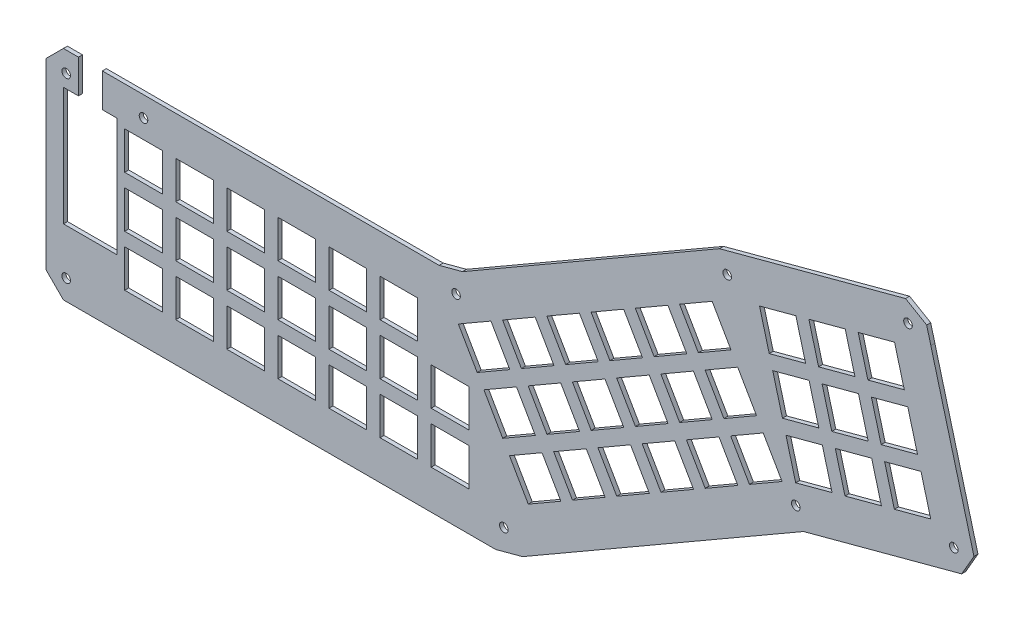
SolidWorks part; units mm, degrees
ref_plane "Plan de face" through (0, 0, 0) normal (0, 0, 1) x (1, 0, 0)
ref_plane "Plan de dessus" through (0, 0, 0) normal (0, 1, 0) x (1, 0, 0)
ref_plane "Plan de droite" through (0, 0, 0) normal (1, 0, 0) x (0, 0, -1)
sketch "Esquisse1" plane through (0, 0, 0) normal (0, 0, 1) x (1, 0, 0)
  line L0 (-73.9886, 18.0851) -> (-59.9886, 18.0851)
  line L1 (-73.9886, 37.0851) -> (-59.9886, 37.0851)
  line L2 (-73.9886, 37.0851) -> (-73.9886, 23.0851)
  line L3 (-73.9886, 23.0851) -> (-59.9886, 23.0851)
  line L4 (-59.9886, 37.0851) -> (-59.9886, 23.0851)
  line L5 (-73.9886, 18.0851) -> (-73.9886, 4.0851)
  line L6 (-73.9886, 4.0851) -> (-59.9886, 4.0851)
  line L7 (-59.9886, 18.0851) -> (-59.9886, 4.0851)
  line L8 (-73.9886, -0.9149) -> (-59.9886, -0.9149)
  line L9 (-73.9886, -0.9149) -> (-73.9886, -14.9149)
  line L10 (-73.9886, -14.9149) -> (-59.9886, -14.9149)
  line L11 (-59.9886, -0.9149) -> (-59.9886, -14.9149)
  line L12 (-73.9886, 37.0851) -> (-73.9886, 18.0851) construction
  line L13 (-54.9886, 18.0851) -> (-40.9886, 18.0851)
  line L14 (-54.9886, 37.0851) -> (-40.9886, 37.0851)
  line L15 (-54.9886, 37.0851) -> (-54.9886, 23.0851)
  line L16 (-54.9886, 23.0851) -> (-40.9886, 23.0851)
  line L17 (-40.9886, 37.0851) -> (-40.9886, 23.0851)
  line L18 (-54.9886, 18.0851) -> (-54.9886, 4.0851)
  line L19 (-54.9886, 4.0851) -> (-40.9886, 4.0851)
  line L20 (-40.9886, 18.0851) -> (-40.9886, 4.0851)
  line L21 (-54.9886, -0.9149) -> (-40.9886, -0.9149)
  line L22 (-54.9886, -0.9149) -> (-54.9886, -14.9149)
  line L23 (-54.9886, -14.9149) -> (-40.9886, -14.9149)
  line L24 (-40.9886, -0.9149) -> (-40.9886, -14.9149)
  line L25 (-54.9886, 37.0851) -> (-54.9886, 18.0851) construction
  line L26 (-35.9886, 18.0851) -> (-21.9886, 18.0851)
  line L27 (-35.9886, 37.0851) -> (-21.9886, 37.0851)
  line L28 (-35.9886, 37.0851) -> (-35.9886, 23.0851)
  line L29 (-35.9886, 23.0851) -> (-21.9886, 23.0851)
  line L30 (-21.9886, 37.0851) -> (-21.9886, 23.0851)
  line L31 (-35.9886, 18.0851) -> (-35.9886, 4.0851)
  line L32 (-35.9886, 4.0851) -> (-21.9886, 4.0851)
  line L33 (-21.9886, 18.0851) -> (-21.9886, 4.0851)
  line L34 (-35.9886, -0.9149) -> (-21.9886, -0.9149)
  line L35 (-35.9886, -0.9149) -> (-35.9886, -14.9149)
  line L36 (-35.9886, -14.9149) -> (-21.9886, -14.9149)
  line L37 (-21.9886, -0.9149) -> (-21.9886, -14.9149)
  line L38 (-35.9886, 37.0851) -> (-35.9886, 18.0851) construction
  line L39 (-16.9886, 18.0851) -> (-2.9886, 18.0851)
  line L40 (-16.9886, 37.0851) -> (-2.9886, 37.0851)
  line L41 (-16.9886, 37.0851) -> (-16.9886, 23.0851)
  line L42 (-16.9886, 23.0851) -> (-2.9886, 23.0851)
  line L43 (-2.9886, 37.0851) -> (-2.9886, 23.0851)
  line L44 (-16.9886, 18.0851) -> (-16.9886, 4.0851)
  line L45 (-16.9886, 4.0851) -> (-2.9886, 4.0851)
  line L46 (-2.9886, 18.0851) -> (-2.9886, 4.0851)
  line L47 (-16.9886, -0.9149) -> (-2.9886, -0.9149)
  line L48 (-16.9886, -0.9149) -> (-16.9886, -14.9149)
  line L49 (-16.9886, -14.9149) -> (-2.9886, -14.9149)
  line L50 (-2.9886, -0.9149) -> (-2.9886, -14.9149)
  line L51 (-16.9886, 37.0851) -> (-16.9886, 18.0851) construction
  line L52 (2.0114, 18.0851) -> (16.0114, 18.0851)
  line L53 (2.0114, 37.0851) -> (16.0114, 37.0851)
  line L54 (2.0114, 37.0851) -> (2.0114, 23.0851)
  line L55 (2.0114, 23.0851) -> (16.0114, 23.0851)
  line L56 (16.0114, 37.0851) -> (16.0114, 23.0851)
  line L57 (2.0114, 18.0851) -> (2.0114, 4.0851)
  line L58 (2.0114, 4.0851) -> (16.0114, 4.0851)
  line L59 (16.0114, 18.0851) -> (16.0114, 4.0851)
  line L60 (2.0114, -0.9149) -> (16.0114, -0.9149)
  line L61 (2.0114, -0.9149) -> (2.0114, -14.9149)
  line L62 (2.0114, -14.9149) -> (16.0114, -14.9149)
  line L63 (16.0114, -0.9149) -> (16.0114, -14.9149)
  line L64 (2.0114, 37.0851) -> (2.0114, 18.0851) construction
  line L65 (21.0114, 18.0851) -> (35.0114, 18.0851)
  line L66 (21.0114, 37.0851) -> (35.0114, 37.0851)
  line L67 (21.0114, 37.0851) -> (21.0114, 23.0851)
  line L68 (21.0114, 23.0851) -> (35.0114, 23.0851)
  line L69 (35.0114, 37.0851) -> (35.0114, 23.0851)
  line L70 (21.0114, 18.0851) -> (21.0114, 4.0851)
  line L71 (21.0114, 4.0851) -> (35.0114, 4.0851)
  line L72 (35.0114, 18.0851) -> (35.0114, 4.0851)
  line L73 (21.0114, -0.9149) -> (35.0114, -0.9149)
  line L74 (21.0114, -0.9149) -> (21.0114, -14.9149)
  line L75 (21.0114, -14.9149) -> (35.0114, -14.9149)
  line L76 (35.0114, -0.9149) -> (35.0114, -14.9149)
  line L77 (21.0114, 37.0851) -> (21.0114, 18.0851) construction
  line L78 (40.0114, 18.0851) -> (54.0114, 18.0851)
  line L79 (40.0114, 37.0851) -> (54.0114, 37.0851) construction
  line L80 (40.0114, 37.0851) -> (40.0114, 23.0851) construction
  line L81 (40.0114, 23.0851) -> (54.0114, 23.0851) construction
  line L82 (54.0114, 37.0851) -> (54.0114, 23.0851) construction
  line L83 (40.0114, 18.0851) -> (40.0114, 4.0851)
  line L84 (40.0114, 4.0851) -> (54.0114, 4.0851)
  line L85 (54.0114, 18.0851) -> (54.0114, 4.0851)
  line L86 (40.0114, -0.9149) -> (54.0114, -0.9149)
  line L87 (40.0114, -0.9149) -> (40.0114, -14.9149)
  line L88 (40.0114, -14.9149) -> (54.0114, -14.9149)
  line L89 (54.0114, -0.9149) -> (54.0114, -14.9149)
  line L90 (40.0114, 37.0851) -> (40.0114, 18.0851) construction
  line L91 (-73.9886, 18.0851) -> (-54.9886, 18.0851) construction
  line L92 (56.0114, 20.0851) -> (56.7532, 18.8002) construction
  line L93 (38.0114, 39.0851) -> (56.0114, 39.0851) construction
  line L94 (56.0114, 39.0851) -> (56.0114, 21.0851) construction
  line L95 (38.0114, 21.0851) -> (56.0114, 21.0851) construction
  line L96 (38.0114, 39.0851) -> (38.0114, 21.0851) construction
  line L97 (19.0114, 39.0851) -> (37.0114, 39.0851) construction
  line L98 (37.0114, 39.0851) -> (37.0114, 21.0851) construction
  line L99 (19.0114, 21.0851) -> (37.0114, 21.0851) construction
  line L100 (19.0114, 39.0851) -> (19.0114, 21.0851) construction
  line L101 (79.4363, 55.512) -> (88.4363, 39.9235) construction
  line L102 (88.4363, 39.9235) -> (72.8478, 30.9235) construction
  line L103 (63.8478, 46.512) -> (72.8478, 30.9235) construction
  line L104 (79.4363, 55.512) -> (63.8478, 46.512) construction
  line L105 (62.9818, 46.012) -> (71.9818, 30.4235) construction
  line L106 (71.9818, 30.4235) -> (56.3933, 21.4235) construction
  line L107 (47.3933, 37.012) -> (56.3933, 21.4235) construction
  line L108 (62.9818, 46.012) -> (47.3933, 37.012) construction
  line L109 (164.2542, 60.603) -> (148.6657, 51.603) construction
  line L110 (62.2497, 43.2799) -> (71.7497, 26.8254) construction
  line L111 (78.7042, 52.7799) -> (88.2042, 36.3254) construction
  line L112 (95.1587, 62.2799) -> (104.6587, 45.8254) construction
  line L113 (111.6132, 71.7799) -> (121.1132, 55.3254) construction
  line L114 (128.0677, 81.2799) -> (137.5677, 64.8254) construction
  line L115 (144.5221, 90.7799) -> (154.0221, 74.3254) construction
  line L116 (148.6657, 51.603) -> (157.6657, 36.0146) construction
  line L117 (69.1254, 3.371) -> (76.1254, -8.7534)
  line L118 (88.2497, -1.7534) -> (76.1254, -8.7534)
  line L119 (81.2497, 10.371) -> (88.2497, -1.7534)
  line L120 (81.2497, 10.371) -> (69.1254, 3.371)
  line L121 (59.6254, 19.8254) -> (66.6254, 7.7011)
  line L122 (78.7497, 14.7011) -> (66.6254, 7.7011)
  line L123 (71.7497, 26.8254) -> (78.7497, 14.7011)
  line L124 (50.1254, 36.2799) -> (57.1254, 24.1556)
  line L125 (69.2497, 31.1556) -> (57.1254, 24.1556)
  line L126 (62.2497, 43.2799) -> (69.2497, 31.1556)
  line L127 (62.2497, 43.2799) -> (50.1254, 36.2799)
  line L128 (71.7497, 26.8254) -> (59.6254, 19.8254)
  line L129 (85.5799, 12.871) -> (92.5799, 0.7466)
  line L130 (104.7042, 7.7466) -> (92.5799, 0.7466)
  line L131 (97.7042, 19.871) -> (104.7042, 7.7466)
  line L132 (97.7042, 19.871) -> (85.5799, 12.871)
  line L133 (76.0799, 29.3254) -> (83.0799, 17.2011)
  line L134 (95.2042, 24.2011) -> (83.0799, 17.2011)
  line L135 (88.2042, 36.3254) -> (95.2042, 24.2011)
  line L136 (66.5799, 45.7799) -> (73.5799, 33.6556)
  line L137 (85.7042, 40.6556) -> (73.5799, 33.6556)
  line L138 (78.7042, 52.7799) -> (85.7042, 40.6556)
  line L139 (78.7042, 52.7799) -> (66.5799, 45.7799)
  line L140 (88.2042, 36.3254) -> (76.0799, 29.3254)
  line L141 (102.0343, 22.371) -> (109.0343, 10.2466)
  line L142 (121.1587, 17.2466) -> (109.0343, 10.2466)
  line L143 (114.1587, 29.371) -> (121.1587, 17.2466)
  line L144 (114.1587, 29.371) -> (102.0343, 22.371)
  line L145 (92.5343, 38.8254) -> (99.5343, 26.7011)
  line L146 (111.6587, 33.7011) -> (99.5343, 26.7011)
  line L147 (104.6587, 45.8254) -> (111.6587, 33.7011)
  line L148 (83.0343, 55.2799) -> (90.0343, 43.1556)
  line L149 (102.1587, 50.1556) -> (90.0343, 43.1556)
  line L150 (95.1587, 62.2799) -> (102.1587, 50.1556)
  line L151 (95.1587, 62.2799) -> (83.0343, 55.2799)
  line L152 (104.6587, 45.8254) -> (92.5343, 38.8254)
  line L153 (118.4888, 31.871) -> (125.4888, 19.7466)
  line L154 (137.6132, 26.7466) -> (125.4888, 19.7466)
  line L155 (130.6132, 38.871) -> (137.6132, 26.7466)
  line L156 (130.6132, 38.871) -> (118.4888, 31.871)
  line L157 (108.9888, 48.3254) -> (115.9888, 36.2011)
  line L158 (128.1132, 43.2011) -> (115.9888, 36.2011)
  line L159 (121.1132, 55.3254) -> (128.1132, 43.2011)
  line L160 (99.4888, 64.7799) -> (106.4888, 52.6556)
  line L161 (118.6132, 59.6556) -> (106.4888, 52.6556)
  line L162 (111.6132, 71.7799) -> (118.6132, 59.6556)
  line L163 (111.6132, 71.7799) -> (99.4888, 64.7799)
  line L164 (121.1132, 55.3254) -> (108.9888, 48.3254)
  line L165 (134.9433, 41.371) -> (141.9433, 29.2466)
  line L166 (154.0677, 36.2466) -> (141.9433, 29.2466)
  line L167 (147.0677, 48.371) -> (154.0677, 36.2466)
  line L168 (147.0677, 48.371) -> (134.9433, 41.371)
  line L169 (125.4433, 57.8254) -> (132.4433, 45.7011)
  line L170 (144.5677, 52.7011) -> (132.4433, 45.7011)
  line L171 (137.5677, 64.8254) -> (144.5677, 52.7011)
  line L172 (115.9433, 74.2799) -> (122.9433, 62.1556)
  line L173 (135.0677, 69.1556) -> (122.9433, 62.1556)
  line L174 (128.0677, 81.2799) -> (135.0677, 69.1556)
  line L175 (128.0677, 81.2799) -> (115.9433, 74.2799)
  line L176 (137.5677, 64.8254) -> (125.4433, 57.8254)
  line L177 (151.3978, 50.871) -> (158.3978, 38.7466)
  line L178 (170.5221, 45.7466) -> (158.3978, 38.7466)
  line L179 (163.5221, 57.871) -> (170.5221, 45.7466)
  line L180 (163.5221, 57.871) -> (151.3978, 50.871)
  line L181 (141.8978, 67.3254) -> (148.8978, 55.2011)
  line L182 (161.0221, 62.2011) -> (148.8978, 55.2011)
  line L183 (154.0221, 74.3254) -> (161.0221, 62.2011)
  line L184 (132.3978, 83.7799) -> (139.3978, 71.6556)
  line L185 (151.5221, 78.6556) -> (139.3978, 71.6556)
  line L186 (144.5221, 90.7799) -> (151.5221, 78.6556)
  line L187 (144.5221, 90.7799) -> (132.3978, 83.7799)
  line L188 (154.0221, 74.3254) -> (141.8978, 67.3254)
  line L189 (173.2542, 45.0146) -> (157.6657, 36.0146) construction
  line L190 (164.2542, 60.603) -> (173.2542, 45.0146) construction
  line L191 (178.3169, 34.0986) -> (169.0534, 56.4627) construction
  line L192 (169.5193, 62.7839) -> (174.1781, 45.3972) construction
  line L193 (174.1781, 45.3972) -> (191.5647, 50.056) construction
  line L194 (186.906, 67.4426) -> (191.5647, 50.056) construction
  line L195 (162.1337, 98.0749) -> (167.0513, 79.7223) construction
  line L196 (169.5193, 62.7839) -> (186.906, 67.4426) construction
  line L197 (167.0513, 79.7223) -> (180.5742, 83.3457)
  line L198 (162.1337, 98.0749) -> (175.6567, 101.6983)
  line L199 (162.1337, 98.0749) -> (165.7572, 84.5519)
  line L200 (165.7572, 84.5519) -> (179.2801, 88.1754)
  line L201 (175.6567, 101.6983) -> (179.2801, 88.1754)
  line L202 (167.0513, 79.7223) -> (170.6747, 66.1993)
  line L203 (170.6747, 66.1993) -> (184.1977, 69.8228)
  line L204 (180.5742, 83.3457) -> (184.1977, 69.8228)
  line L205 (171.9688, 61.3697) -> (185.4918, 64.9932)
  line L206 (171.9688, 61.3697) -> (175.5923, 47.8467)
  line L207 (175.5923, 47.8467) -> (189.1152, 51.4702)
  line L208 (185.4918, 64.9932) -> (189.1152, 51.4702)
  line L209 (185.4038, 84.6398) -> (198.9268, 88.2633)
  line L210 (180.4863, 102.9924) -> (194.0092, 106.6159)
  line L211 (180.4863, 102.9924) -> (184.1097, 89.4695)
  line L212 (184.1097, 89.4695) -> (197.6327, 93.0929)
  line L213 (194.0092, 106.6159) -> (197.6327, 93.0929)
  line L214 (185.4038, 84.6398) -> (189.0273, 71.1169)
  line L215 (189.0273, 71.1169) -> (202.5503, 74.7403)
  line L216 (198.9268, 88.2633) -> (202.5503, 74.7403)
  line L217 (190.3214, 66.2873) -> (203.8444, 69.9107)
  line L218 (190.3214, 66.2873) -> (193.9449, 52.7643)
  line L219 (193.9449, 52.7643) -> (207.4678, 56.3878)
  line L220 (203.8444, 69.9107) -> (207.4678, 56.3878)
  line L221 (187.8719, 67.7015) -> (192.5307, 50.3148) construction
  line L222 (192.5307, 50.3148) -> (209.9173, 54.9735) construction
  line L223 (205.2586, 72.3602) -> (209.9173, 54.9735) construction
  line L224 (180.4863, 102.9924) -> (185.4038, 84.6398) construction
  line L225 (187.8719, 67.7015) -> (205.2586, 72.3602) construction
  line L226 (203.7564, 89.5574) -> (217.2794, 93.1809)
  line L227 (198.8389, 107.91) -> (212.3618, 111.5335)
  line L228 (198.8389, 107.91) -> (202.4623, 94.387)
  line L229 (202.4623, 94.387) -> (215.9853, 98.0105)
  line L230 (212.3618, 111.5335) -> (215.9853, 98.0105)
  line L231 (203.7564, 89.5574) -> (207.3799, 76.0344)
  line L232 (207.3799, 76.0344) -> (220.9029, 79.6579)
  line L233 (217.2794, 93.1809) -> (220.9029, 79.6579)
  line L234 (208.674, 71.2048) -> (222.197, 74.8283)
  line L235 (208.674, 71.2048) -> (212.2975, 57.6819)
  line L236 (212.2975, 57.6819) -> (225.8204, 61.3053)
  line L237 (222.197, 74.8283) -> (225.8204, 61.3053)
  line L238 (206.2245, 72.619) -> (210.8833, 55.2324) construction
  line L239 (210.8833, 55.2324) -> (228.2699, 59.8911) construction
  line L240 (223.6112, 77.2778) -> (228.2699, 59.8911) construction
  line L241 (198.8389, 107.91) -> (203.7564, 89.5574) construction
  line L242 (206.2245, 72.619) -> (223.6112, 77.2778) construction
  line L243 (167.0513, 79.7223) -> (185.4038, 84.6398) construction
  line L244 (38.0114, 20.0851) -> (56.0114, 20.0851) construction
  line L245 (56.0114, 20.0851) -> (56.0114, 2.0851) construction
  line L246 (38.0114, 2.0851) -> (56.0114, 2.0851) construction
  line L247 (38.0114, 20.0851) -> (38.0114, 2.0851) construction
  line L248 (72.4818, 29.5575) -> (56.8933, 20.5575) construction
  line L249 (56.8933, 20.5575) -> (65.8933, 4.969) construction
  line L250 (81.4818, 13.969) -> (65.8933, 4.969) construction
  line L251 (72.4818, 29.5575) -> (81.4818, 13.969) construction
  line L252 (56.8933, 20.5575) -> (57.6111, 19.3142) construction
  line L253 (164.6018, 81.1365) -> (169.2605, 63.7498) construction
  line L254 (169.2605, 63.7498) -> (186.6472, 68.4086) construction
  line L255 (181.9884, 85.7952) -> (186.6472, 68.4086) construction
  line L256 (164.6018, 81.1365) -> (181.9884, 85.7952) construction
  line L257 (154.7542, 77.0575) -> (163.7542, 61.469) construction
  line L258 (163.7542, 61.469) -> (148.1657, 52.469) construction
  line L259 (139.1657, 68.0575) -> (148.1657, 52.469) construction
  line L260 (154.7542, 77.0575) -> (139.1657, 68.0575) construction
  line L261 (196.3894, 109.3242) -> (213.776, 113.983) construction
  line L262 (-94.7538, 35.7952) -> (-76.7538, 35.7952) construction
  line L263 (-94.7538, 35.7952) -> (-94.7538, 2.7952) construction
  line L264 (-94.7538, 2.7952) -> (-76.7538, 2.7952) construction
  line L265 (-76.7538, 35.7952) -> (-76.7538, 2.7952) construction
  line L266 (213.776, 113.983) -> (218.4348, 96.5963) construction
  line L267 (201.0481, 91.9375) -> (218.4348, 96.5963) construction
  line L268 (196.3894, 109.3242) -> (201.0481, 91.9375) construction
  line L269 (-75.9886, -16.9149) -> (-57.9886, -16.9149) construction
  line L270 (-57.9886, 1.0851) -> (-57.9886, -16.9149) construction
  line L271 (-75.9886, 1.0851) -> (-57.9886, 1.0851) construction
  line L272 (-75.9886, 1.0851) -> (-75.9886, -16.9149) construction
  line L273 (38.0114, -16.9149) -> (56.0114, -16.9149) construction
  line L274 (56.0114, 1.0851) -> (56.0114, -16.9149) construction
  line L275 (38.0114, 1.0851) -> (56.0114, 1.0851) construction
  line L276 (38.0114, 1.0851) -> (38.0114, -16.9149) construction
  line L277 (-75.9886, 39.0851) -> (-57.9886, 39.0851) construction
  line L278 (-57.9886, 39.0851) -> (-57.9886, 21.0851) construction
  line L279 (-75.9886, 21.0851) -> (-57.9886, 21.0851) construction
  line L280 (-75.9886, 39.0851) -> (-75.9886, 21.0851) construction
  line L281 (145.2542, 93.512) -> (129.6657, 84.512) construction
  line L282 (129.6657, 84.512) -> (138.6657, 68.9235) construction
  line L283 (154.2542, 77.9235) -> (138.6657, 68.9235) construction
  line L284 (145.2542, 93.512) -> (154.2542, 77.9235) construction
  line L285 (223.4353, 116.5711) -> (228.0941, 99.1845) construction
  line L286 (148.2159, 106.7689) -> (211.1879, 123.6422) construction
  line L287 (177.5508, 35.9482) -> (235.6877, 51.5259) construction
  line L288 (177.5508, 35.9482) -> (72.9989, -24.4149) construction
  line L289 (-95.7538, -26.9149) -> (63.6687, -26.9149) construction
  line L290 (-100.7538, 35.7952) -> (-100.7538, -21.9149) construction
  line L291 (-75.9886, 49.0851) -> (43.3046, 49.0851) construction
  line L292 (148.2159, 106.7689) -> (52.6347, 51.5851) construction
  line L293 (-75.9886, 49.0851) -> (-57.9886, 49.0851) construction
  line L294 (140.2542, 102.1722) -> (124.6657, 93.1722) construction
  line L295 (193.8012, 118.9835) -> (211.1879, 123.6422) construction
  line L296 (213.4714, 45.5731) -> (230.8581, 50.2318) construction
  line L297 (38.0114, -26.9149) -> (38.0114, -85.4624) construction
  line L298 (178.2542, 36.3543) -> (162.6657, 27.3543) construction
  line L299 (38.0114, -26.9149) -> (56.0114, -26.9149) construction
  line L300 (-100.7538, 2.7952) -> (-100.7538, -38.0419) construction
  line L301 (-100.7538, 35.7952) -> (-100.7538, 2.7952) construction
  line L302 (-75.9886, 49.0851) -> (-95.7538, 49.0851) construction
  line L303 (-100.7538, 44.0851) -> (-100.7538, 35.7952) construction
  line L304 (211.1879, 123.6422) -> (216.0732, 124.9512) construction
  line L305 (222.1691, 121.4083) -> (223.4353, 116.5711) construction
  line L306 (228.0941, 99.1845) -> (239.2233, 57.6497) construction
  line L307 (216.0732, 124.9512) -> (222.1691, 121.4083) construction
  line L308 (235.6877, 51.5259) -> (239.2233, 57.6497) construction
  line L309 (63.6687, -26.9149) -> (72.9989, -24.4149) construction
  line L310 (52.6347, 51.5851) -> (43.3046, 49.0851) construction
  line L311 (-95.7538, 49.0851) -> (-100.7538, 44.0851) construction
  line L312 (-100.7538, -21.9149) -> (-95.7538, -26.9149) construction
  line L313 (-95.7538, 49.0851) -> (-95.7538, 44.0851) construction
  line L314 (-95.7538, 44.0851) -> (-100.7538, 44.0851) construction
  line L315 (-95.7538, -26.9149) -> (-95.7538, -21.9149) construction
  line L316 (68.3338, -25.6649) -> (67.0397, -20.8353) construction
  line L317 (47.9697, 50.3351) -> (49.2637, 45.5055) construction
  line L318 (177.5508, 35.9482) -> (175.6374, 40.5676) construction
  line L319 (148.2159, 106.7689) -> (150.1293, 102.1495) construction
  line L320 (239.2233, 57.6497) -> (234.3936, 56.3556) construction
  line L321 (216.0732, 124.9512) -> (217.3634, 120.1206) construction
  line L322 (-66.9886, 37.0851) -> (-66.9886, 49.0851) construction
  line L323 (-76.7538, 35.7952) -> (-96.7538, 35.7952) construction
  line L324 (-95.7538, 44.0851) -> (-65.1374, 44.0851) construction
  line L325 (-76.7538, 39.0851) -> (-82.31, 39.0851)
  line L326 (-76.7538, 39.0851) -> (-76.7538, -4.9149)
  line L327 (-76.7538, 1.0851) -> (-96.7538, 1.0851) construction
  line L328 (-96.7538, 39.0851) -> (-96.7538, -4.9149)
  line L329 (-75.9886, 50.5851) -> (43.1071, 50.5851) construction
  line L330 (52.0557, 52.9829) -> (43.1071, 50.5851) construction
  line L331 (147.6369, 108.1667) -> (52.0557, 52.9829) construction
  line L332 (147.6369, 108.1667) -> (210.7996, 125.0911) construction
  line L333 (210.7996, 125.0911) -> (216.2876, 126.5616) construction
  line L334 (216.2876, 126.5616) -> (223.4622, 122.3917) construction
  line L335 (223.4622, 122.3917) -> (224.8853, 116.9552) construction
  line L336 (224.8853, 116.9552) -> (229.5429, 99.5727) construction
  line L337 (229.5429, 99.5727) -> (240.833, 57.4377) construction
  line L338 (236.6761, 50.2379) -> (240.833, 57.4377) construction
  line L339 (178.1298, 34.5504) -> (236.6761, 50.2379) construction
  line L340 (178.1298, 34.5504) -> (73.5778, -25.8127) construction
  line L341 (63.8662, -28.4149) -> (73.5778, -25.8127) construction
  line L342 (-96.3751, -28.4149) -> (63.8662, -28.4149) construction
  line L343 (-102.2538, -22.5362) -> (-96.3751, -28.4149) construction
  line L344 (-102.2538, 35.7952) -> (-102.2538, -22.5362) construction
  line L345 (-102.2538, 44.7064) -> (-102.2538, 35.7952) construction
  line L346 (-96.3751, 50.5851) -> (-102.2538, 44.7064) construction
  line L347 (-75.9886, 50.5851) -> (-96.3751, 50.5851) construction
  line L348 (-75.9886, 52.5851) -> (42.8438, 52.5851) construction
  line L349 (51.2838, 54.8466) -> (42.8438, 52.5851) construction
  line L350 (146.8649, 110.0304) -> (51.2838, 54.8466) construction
  line L351 (146.8649, 110.0304) -> (210.282, 127.023) construction
  line L352 (210.282, 127.023) -> (216.5734, 128.7087) construction
  line L353 (216.5734, 128.7087) -> (225.1863, 123.7029) construction
  line L354 (225.1863, 123.7029) -> (226.8187, 117.4673) construction
  line L355 (226.8187, 117.4673) -> (231.4748, 100.0903) construction
  line L356 (231.4748, 100.0903) -> (242.9792, 57.1552) construction
  line L357 (237.994, 48.5204) -> (242.9792, 57.1552) construction
  line L358 (178.9017, 32.6867) -> (237.994, 48.5204) construction
  line L359 (178.9017, 32.6867) -> (74.3498, -27.6764) construction
  line L360 (64.1295, -30.4149) -> (74.3498, -27.6764) construction
  line L361 (-97.2035, -30.4149) -> (64.1295, -30.4149) construction
  line L362 (-104.2538, -23.3646) -> (-97.2035, -30.4149) construction
  line L363 (-104.2538, 35.7952) -> (-104.2538, -23.3646) construction
  line L364 (-104.2538, 45.5349) -> (-104.2538, 35.7952) construction
  line L365 (-97.2035, 52.5851) -> (-104.2538, 45.5349) construction
  line L366 (-75.9886, 52.5851) -> (-97.2035, 52.5851) construction
  line L367 (-75.9886, 51.5851) -> (42.9755, 51.5851)
  line L368 (51.6698, 53.9147) -> (42.9755, 51.5851)
  line L369 (147.2509, 109.0986) -> (51.6698, 53.9147)
  line L370 (147.2509, 109.0986) -> (210.5408, 126.057)
  line L371 (210.5408, 126.057) -> (216.4305, 127.6352)
  line L372 (216.4305, 127.6352) -> (224.3243, 123.0473)
  line L373 (224.3243, 123.0473) -> (225.852, 117.2112)
  line L374 (225.852, 117.2112) -> (230.5089, 99.8315)
  line L375 (230.5089, 99.8315) -> (241.9061, 57.2965)
  line L376 (237.335, 49.3791) -> (241.9061, 57.2965)
  line L377 (178.5158, 33.6186) -> (237.335, 49.3791)
  line L378 (178.5158, 33.6186) -> (73.9638, -26.7445)
  line L379 (63.9979, -29.4149) -> (73.9638, -26.7445)
  line L380 (-96.7893, -29.4149) -> (63.9979, -29.4149)
  line L381 (-103.2538, -22.9504) -> (-96.7893, -29.4149)
  line L382 (-103.2538, 35.7952) -> (-103.2538, -22.9504)
  line L383 (-103.2538, 45.1206) -> (-103.2538, 35.7952)
  line L384 (-96.7893, 51.5851) -> (-103.2538, 45.1206)
  line L385 (-75.9886, 51.5851) -> (-82.31, 51.5851)
  line L386 (-86.7538, 39.0851) -> (-86.7538, 51.5851) construction
  line L387 (-91.1976, 39.0851) -> (-91.1976, 51.5851)
  line L388 (-82.31, 39.0851) -> (-82.31, 51.5851)
  line L389 (-91.1976, 51.5851) -> (-96.7893, 51.5851)
  line L390 (-91.1976, 39.0851) -> (-96.7538, 39.0851)
  line L391 (-75.9886, 51.5851) -> (-96.7893, 51.5851) construction
  line L392 (-76.7538, -4.9149) -> (-96.7538, -4.9149)
  circle A0 centre (-95.7538, 44.0851) radius 1.5 construction
  circle A1 centre (-95.7538, -21.9149) radius 1.5 construction
  circle A2 centre (67.0397, -20.8353) radius 1.5 construction
  circle A3 centre (49.2637, 45.5055) radius 1.5 construction
  circle A4 centre (175.6374, 40.5676) radius 1.5 construction
  circle A5 centre (150.1293, 102.1495) radius 1.5 construction
  circle A6 centre (234.3936, 56.3556) radius 1.5 construction
  circle A7 centre (217.3634, 120.1206) radius 1.5 construction
  circle A8 centre (-66.9886, 44.0851) radius 1.5 construction
  circle A9 centre (-95.7538, 44.0851) radius 1.6
  circle A10 centre (-66.9886, 44.0851) radius 1.6
  circle A11 centre (-95.7538, -21.9149) radius 1.6
  circle A12 centre (67.0397, -20.8353) radius 1.6
  circle A13 centre (49.2637, 45.5055) radius 1.6
  circle A14 centre (175.6374, 40.5676) radius 1.6
  circle A15 centre (150.1293, 102.1495) radius 1.6
  circle A16 centre (217.3634, 120.1206) radius 1.6
  circle A17 centre (234.3936, 56.3556) radius 1.6
  point P304 (48.3046, 49.0851)
  point P305 (240.5174, 52.82)
  point P308 (68.6687, -26.9149)
  point P309 (-100.7538, -26.9149)
  point P311 (-100.7538, 49.0851)
  point P312 (220.9029, 126.2453)
  point P430 (-86.7538, 45.3351)
  dimension "D32" = 3
  dimension "D33" = 5
  dimension "D40" = 5
  dimension "D41" = 5
  dimension "D42" = 5
  dimension "D43" = 5
  dimension "D44" = 20
  dimension "D45" = 1.5
  dimension "D49" = 0.1
  dimension "D1" = 14
  dimension "D2" = 14
  dimension "D4" = 19
  dimension "D6" = 19
  dimension "D7" = 30
  dimension "D10" = 1
  dimension "D11" = 2
  dimension "D13" = 0.5
  dimension "D15" = 2
  dimension "D12" = 7.5
  dimension "D14" = 19
  dimension "D18" = 2
  dimension "D20" = 18
  dimension "D21" = 33
  dimension "D22" = 2
  dimension "D8" = 2
  dimension "D9" = 2
  dimension "D16" = 2
  dimension "D19" = 2
  dimension "D23" = 2
  dimension "D24" = 10
  dimension "D25" = 10
  dimension "D26" = 10
  dimension "D27" = 10
  dimension "D28" = 10
  dimension "D29" = 6
  dimension "D30" = 10
  dimension "D31" = 10
  dimension "D46" = 2
  dimension "D47" = 1
  dimension "D48" = 0.1
  dimension "D50" = 6
  dimension "D3" = 3
  dimension "D5" = 7
  dimension "D17" = 3
extrude "Boss.-Extru.1" add sketch "Esquisse1" along normal blind 1.5
